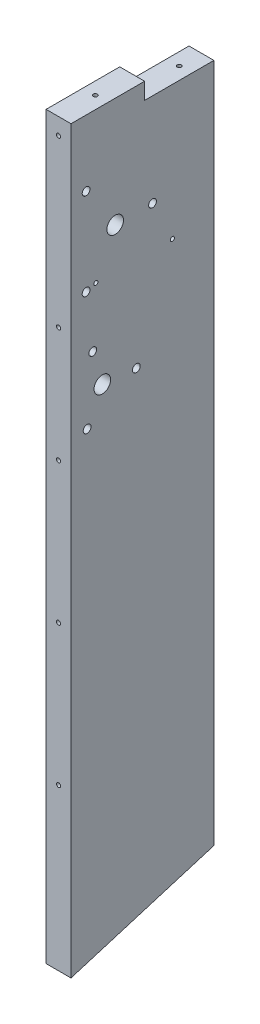
SolidWorks part; units mm, degrees
material "Beech"
ref_plane "Front Plane" through (0, 0, 0) normal (0, 0, 1) x (1, 0, 0)
ref_plane "Top Plane" through (0, 0, 0) normal (0, 1, 0) x (1, 0, 0)
ref_plane "Right Plane" through (0, 0, 0) normal (1, 0, 0) x (0, 0, -1)
sketch "Sketch1" plane through (0, 0, 0) normal (0, 0, 1) x (1, 0, 0)
  line L0 (-331.7795, -427.3421) -> (-331.7795, 0) construction
  line L1 (93.2955, -427.3421) -> (-341.3045, -427.3421) construction
  line L3 (-322.2545, -427.3421) -> (-322.2545, 0)
  line L4 (-341.3045, -427.3421) -> (-341.3045, 0)
  line L5 (-322.2545, -427.3421) -> (-341.3045, -427.3421)
  line L6 (-322.2545, 0) -> (-341.3045, 0)
  line L7 (-341.3045, -427.3421) -> (-341.3045, 12.7) construction
  line L8 (-331.7795, -427.3421) -> (-331.7795, 0) construction
  dimension "D1" = 19.05
extrude "Boss-Extrude1" add sketch "Sketch1" along normal up to surface (53 mm away)
sketch "Sketch2" plane through (0, 0, 53) normal (0, 0, 1) x (1, 0, 0)
  line L0 (-231.3045, 12.7) -> (-341.3045, 12.7) construction
  line L1 (-322.2545, 12.7) -> (-341.3045, 12.7)
  line L4 (-341.3045, 0) -> (-341.3045, -427.3421)
  line L5 (-341.3045, -427.3421) -> (-322.2545, -427.3421)
  line L6 (-322.2545, -427.3421) -> (-322.2545, 0)
  line L7 (-322.2545, 0) -> (-341.3045, 0)
  line L8 (-341.3045, 12.7) -> (-341.3045, -427.3421)
  line L9 (-341.3045, -427.3421) -> (-322.2545, -427.3421)
  line L10 (-322.2545, -427.3421) -> (-322.2545, 12.7)
  dimension "D1" = 0
extrude "Boss-Extrude2" add sketch "Sketch2" along normal up to surface (56.3 mm away)
sketch "Sketch3" plane through (-341.3045, 0, 0) normal (-1, 0, 0) x (0, 0, 1)
  line L0 (0, -427.3421) -> (109.3, -427.3421)
  line L1 (109.3, -427.3421) -> (109.3, -464.2661)
  line L2 (109.3, -464.2661) -> (0, -431.1858)
  line L3 (-12.7, -427.3421) -> (522.1409, -589.2145) construction
  line L4 (0, -431.1858) -> (0, -427.3421)
extrude "Boss-Extrude3" add sketch "Sketch3" against normal through all
hole_wizard "15/64 (0.23438) Diameter Hole1" positions "Sketch5" profile "Sketch6" hole size "15/64" standard "ANSI Inch" end condition through all
sketch "Sketch5" plane through (-341.3045, 0, 0) normal (-1, 0, 0) x (0, 0, 1)
  point P0 (97.7483, -37.836)
  point P3 (97.7483, -104.511)
  point P6 (46.9483, -71.1735)
  point P9 (92.6826, -146.5881)
  point P12 (96.9737, -195.6358)
  point P15 (59.3512, -174.2158)
sketch "Sketch6" plane through (-341.3045, -37.836, 97.7483) normal (0, 1, 0) x (0, 0, 1)
  line L0 (0, 0) -> (0, 19.05)
  line L1 (0, 19.05) -> (2.9766, 19.05)
  line L2 (2.9766, 19.05) -> (2.9766, 0)
  line L5 (2.9766, 0) -> (0, 0)
  line L11 (0, -6.35) -> (0, 107.95) construction
  dimension "Thru Hole Dia." = 5.9533
  dimension "Thru Hole Depth" = 19.05
sketch "Sketch4" plane through (-341.3045, 0, 0) normal (-1, 0, 0) x (0, 0, 1)
  circle A0 centre (75.5233, -71.1735) radius 6.35 construction
  circle A1 centre (75.5233, -71.1735) radius 6.35
  circle A2 centre (85.3394, -171.9421) radius 6.35 construction
  circle A3 centre (85.3394, -171.9421) radius 6.35
extrude "Cut-Extrude1" cut sketch "Sketch4" against normal through all
hole_wizard "Hole1" positions "Sketch7" profile "Sketch8" legacy
sketch "Sketch7" plane through (-124.0045, -78.4757, 122) normal (0, 0, 1) x (-1, 0, 0)
  line L1 (0, 465.9538) -> (0, 66.1243) construction
  line L2 (126.073, 146.2179) -> (113.373, 146.2179) construction
  line L6 (119.723, 195.4304) -> (119.723, 97.0054) construction
  line L10 (68.923, 196.0654) -> (68.923, 111.2929) construction
  point P1 (113.65, 39.9076)
  point P3 (113.65, -64.959)
  point P5 (-94.6, 72.4743)
  point P7 (94.6, 72.4743)
  point P9 (0, 72.4743)
  point P11 (0, 104.2243)
  point P13 (0, 351.6538)
  point P15 (0, 213.0704)
  point P17 (40.9792, 213.0704)
  point P19 (166.7958, 213.0704)
  point P21 (207.775, 351.6538)
  point P23 (207.775, 244.1214)
  point P25 (207.775, 136.589)
  point P27 (207.775, 48.5243)
  point P29 (207.775, -78.4757)
  point P33 (-207.775, -78.4757)
  point P34 (-207.775, 48.5243)
  point P35 (-207.775, 136.589)
  point P36 (-207.775, 244.1214)
  point P37 (-207.775, 351.6538)
  point P38 (-166.7958, 213.0704)
  point P39 (-40.9792, 213.0704)
  point P40 (-113.65, -64.959)
  point P41 (-113.65, 39.9076)
  point P58 (119.723, 146.2179)
  point P65 (119.723, 109.7054)
  point P68 (119.723, 182.7304)
  point P78 (18.123, 109.7054)
  point P79 (18.123, 182.7304)
  point P81 (0, 0)
  point P82 (113.65, 23.941)
  point P83 (0, 0)
  point P84 (207.775, -78.2752)
  point P85 (209.3058, -90.1558)
  point P86 (207.775, -78.4757)
  point P88 (113.65, -64.959)
  point P90 (207.775, 48.5243)
  point P92 (0, 0)
  point P93 (207.775, 136.589)
  point P95 (207.775, 244.1214)
  point P97 (207.775, 351.6538)
  point P99 (113.65, 39.9076)
  point P101 (94.6, 72.4743)
  point P103 (0, 72.4743)
  point P105 (0, 104.2243)
  point P107 (0, 0)
  point P108 (0, 213.0704)
  point P110 (0, 0)
  point P111 (0, 351.6538)
  point P113 (-40.9792, 213.0704)
  point P115 (-94.6, 72.4743)
  point P117 (-166.7958, 213.0704)
  point P119 (-113.65, -64.959)
  point P121 (0, 66.1243)
  dimension "D1" = 12.7
  dimension "D2" = 12.7
sketch "Sketch8" plane through (-237.6545, -118.3833, 122) normal (1, 0, 0) x (0, -1, 0)
  line L0 (0, 0) -> (0, 32.7039)
  line L1 (0, 32.7039) -> (1.5875, 31.75)
  line L2 (1.5875, 31.75) -> (1.5875, 4.0177)
  line L3 (1.5875, 4.0177) -> (5.08, 0)
  line L4 (5.08, 0) -> (0, 0)
  line L5 (0, -14.3089) -> (0, 102.4216) construction
  line L6 (0, 32.7039) -> (-1.5875, 31.75) construction
  line L7 (-1.5875, 4.0177) -> (-5.08, 0) construction
  dimension "Diameter" = 3.175
  dimension "Depth" = 31.75
  dimension "C-Sink Diameter" = 10.16
  dimension "C-Sink Angle" = 82
  dimension "Drill Angle" = 118
hole_wizard "Hole" positions "Sketch9" profile "Sketch10" legacy
sketch "Sketch9" plane through (-124.0045, 25.4, -155.2867) normal (0, 1, 0) x (-1, 0, 0)
  point P0 (113.65, 236.4367)
  point P2 (207.775, 236.4367)
sketch "Sketch10" plane through (-237.6545, 25.4, 81.15) normal (1, 0, 0) x (0, 0, 1)
  line L0 (0, 0) -> (0, 32.7039)
  line L1 (0, 32.7039) -> (1.5875, 31.75)
  line L2 (1.5875, 31.75) -> (1.5875, 4.0177)
  line L3 (1.5875, 4.0177) -> (5.08, 0)
  line L4 (5.08, 0) -> (0, 0)
  line L5 (0, -14.3089) -> (0, 102.4216) construction
  line L6 (0, 32.7039) -> (-1.5875, 31.75) construction
  line L7 (-1.5875, 4.0177) -> (-5.08, 0) construction
  dimension "Diameter" = 3.175
  dimension "Depth" = 31.75
  dimension "C-Sink Diameter" = 10.16
  dimension "C-Sink Angle" = 82
  dimension "Drill Angle" = 118
hole_wizard "Hole3" positions "Sketch12" profile "Sketch13" legacy
sketch "Sketch12" plane through (-124.0045, 12.7, -155.2867) normal (0, 1, 0) x (-1, 0, 0)
  line L0 (120, 172.2617) -> (217.3, 172.2617) construction
  point P8 (126.35, 172.2617)
  point P10 (207.775, 172.2617)
sketch "Sketch13" plane through (-331.7795, 12.7, 16.975) normal (1, 0, 0) x (0, 0, 1)
  line L0 (0, 0) -> (0, 32.7039)
  line L1 (0, 32.7039) -> (1.5875, 31.75)
  line L2 (1.5875, 31.75) -> (1.5875, 4.0177)
  line L3 (1.5875, 4.0177) -> (5.08, 0)
  line L4 (5.08, 0) -> (0, 0)
  line L5 (0, -14.3089) -> (0, 102.4216) construction
  line L6 (0, 32.7039) -> (-1.5875, 31.75) construction
  line L7 (-1.5875, 4.0177) -> (-5.08, 0) construction
  dimension "Diameter" = 3.175
  dimension "Depth" = 31.75
  dimension "C-Sink Diameter" = 10.16
  dimension "C-Sink Angle" = 82
  dimension "Drill Angle" = 118
hole_wizard "Hole4" positions "Sketch14" profile "Sketch15" legacy
sketch "Sketch14" plane through (-124.0045, -78.4757, -12.7) normal (0, 0, -1) x (1, 0, 0)
  line L12 (0, 0) -> (0, 66.1243) construction
  line L17 (120, -84.8257) -> (217.3, -84.8257) construction
  line L21 (-217.3, -84.8257) -> (-120, -84.8257) construction
  point P0 (-207.775, 244.1214)
  point P3 (-207.775, 136.589)
  point P6 (-207.775, 48.5243)
  point P9 (-185.55, -84.8257)
  point P12 (-151.75, -84.8257)
  point P15 (-94.6, 72.4743)
  point P21 (94.6, 72.4743)
  point P24 (151.75, -84.8257)
  point P27 (185.55, -84.8257)
  point P30 (207.775, 48.5243)
  point P33 (207.775, 136.589)
  point P36 (207.775, 244.1214)
  point P39 (166.7958, 213.0704)
  point P42 (40.9792, 213.0704)
  point P45 (-40.9792, 213.0704)
  point P48 (-166.7958, 213.0704)
  point P51 (0, 104.2243)
  point P54 (0, 213.0704)
  point P57 (0, 323.4664)
  point P80 (-126.35, 34.5243)
  point P82 (-126.35, -46.8757)
  point P96 (126.35, -46.8757)
  point P97 (126.35, 34.5243)
  dimension "D4" = 31.75
  dimension "D5" = 31.75
sketch "Sketch15" plane through (-331.7795, -322.5971, -12.7) normal (1, 0, 0) x (0, 1, 0)
  line L0 (0, 0) -> (0, 32.7039)
  line L1 (0, 32.7039) -> (1.5875, 31.75)
  line L2 (1.5875, 31.75) -> (1.5875, 4.0177)
  line L3 (1.5875, 4.0177) -> (5.08, 0)
  line L4 (5.08, 0) -> (0, 0)
  line L5 (0, -14.3089) -> (0, 102.4216) construction
  line L6 (0, 32.7039) -> (-1.5875, 31.75) construction
  line L7 (-1.5875, 4.0177) -> (-5.08, 0) construction
  dimension "Diameter" = 3.175
  dimension "Depth" = 31.75
  dimension "C-Sink Diameter" = 10.16
  dimension "C-Sink Angle" = 82
  dimension "Drill Angle" = 118
hole_wizard "Hole5" positions "Sketch16" profile "Sketch17" legacy rebuild error yes
sketch "Sketch16" plane through (-124.0045, -452.1296, -268.3751) normal (0, -0.9571, -0.2897) x (1, 0, 0)
  line L4 (-207.775, 822.0847) -> (-207.775, 404.0189) construction
  line L8 (-207.775, 822.0847) -> (-207.775, 717.5683)
  line L9 (-207.775, 717.5683) -> (-207.775, 613.0518)
  line L10 (-207.775, 613.0518) -> (-207.775, 508.5353)
  line L11 (-207.775, 508.5353) -> (-207.775, 404.0189)
  line L12 (-108.65, 822.0847) -> (-108.65, 404.0189) construction
  line L15 (0, 822.0847) -> (0, 613.0518) construction
  line L18 (-207.775, 388.2192) -> (-207.775, 263.2847) construction
  line L22 (-207.775, 388.2192) -> (-207.775, 356.9856)
  line L23 (-207.775, 356.9856) -> (-207.775, 325.752)
  line L24 (-207.775, 325.752) -> (-207.775, 294.5183)
  line L25 (-207.775, 294.5183) -> (-207.775, 263.2847)
  line L26 (0, 388.2192) -> (0, 263.2847) construction
  line L30 (0, 263.2847) -> (0, 294.5183)
  line L31 (0, 294.5183) -> (0, 325.752)
  line L32 (0, 325.752) -> (0, 356.9856)
  line L33 (0, 356.9856) -> (0, 388.2192)
  point P24 (-207.775, 613.0518)
  point P31 (-207.775, 456.2771)
  point P33 (-207.775, 769.8265)
  point P52 (-108.65, 456.2771)
  point P54 (-108.65, 630.1265)
  point P56 (-108.65, 769.8265)
  point P76 (-207.775, 356.9856)
  point P80 (-207.775, 294.5183)
  point P99 (0, 294.5183)
  point P104 (0, 356.9856)
  point P113 (207.775, 294.5183)
  point P114 (207.775, 356.9856)
  point P115 (108.65, 769.8265)
  point P116 (108.65, 630.1265)
  point P117 (108.65, 456.2771)
  point P118 (207.775, 769.8265)
  point P119 (207.775, 456.2771)
  point P120 (207.775, 613.0518)
  dimension "D1" = 139.7
sketch "Sketch17" plane through (83.7705, -629.7176, 318.3915) normal (1, 0, 0) x (0, 0.2897, -0.9571)
  line L0 (0, 0) -> (0, 32.7039)
  line L1 (0, 32.7039) -> (1.5875, 31.75)
  line L2 (1.5875, 31.75) -> (1.5875, 4.0177)
  line L3 (1.5875, 4.0177) -> (5.08, 0)
  line L4 (5.08, 0) -> (0, 0)
  line L5 (0, -14.3089) -> (0, 102.4216) construction
  line L6 (0, 32.7039) -> (-1.5875, 31.75) construction
  line L7 (-1.5875, 4.0177) -> (-5.08, 0) construction
  dimension "Diameter" = 3.175
  dimension "Depth" = 31.75
  dimension "C-Sink Diameter" = 10.16
  dimension "C-Sink Angle" = 82
  dimension "Drill Angle" = 118
hole_wizard "Hole6" positions "Sketch18" profile "Sketch19" legacy
sketch "Sketch18" plane through (-354.0045, -78.4757, -155.2867) normal (-1, 0, 0) x (0, -0.9959, 0.09)
  line L0 (47.5949, 261.3648) -> (37.7623, 152.508) construction
  line L6 (451.4691, 193.1171) -> (418.4769, 118.1196) construction
  line L11 (486.2923, 274.2447) -> (514.0528, 264.0879) construction
  line L16 (472.4376, 447.6352) -> (491.8067, 432.4853) construction
  line L19 (635.9114, 629.7221) -> (595.5648, 529.8608) construction
  line L24 (664.0363, 618.3589) -> (454.7061, 100.2486) construction
  line L28 (664.0363, 618.3589) -> (611.7037, 488.8313)
  line L29 (611.7037, 488.8313) -> (559.3712, 359.3037)
  line L30 (559.3712, 359.3037) -> (507.0387, 229.7761)
  line L31 (507.0387, 229.7761) -> (454.7061, 100.2486)
  point P12 (45.8811, 242.3921)
  point P14 (40.6185, 184.1293)
  point P29 (426.1478, 135.557)
  point P31 (446.3552, 181.4922)
  point P48 (500.1726, 269.1663)
  point P79 (628.7751, 612.0592)
  point P81 (602.701, 547.5236)
  point P98 (559.3712, 359.3037)
  point P100 (507.0387, 229.7761)
  point P112 (637.87, 553.5951)
  point P120 (0, 0)
  dimension "D1" = 19.05
  dimension "D2" = 31.75
  dimension "D3" = 12.7
  dimension "D4" = 19.05
  dimension "D5" = 19.05
  dimension "D6" = 19.05
sketch "Sketch19" plane through (-354.0045, -663.9582, 453.4463) normal (0, 1, 0) x (0, 0, 1)
  line L0 (0, 0) -> (0, 32.7039)
  line L1 (0, 32.7039) -> (1.5875, 31.75)
  line L2 (1.5875, 31.75) -> (1.5875, 4.0177)
  line L3 (1.5875, 4.0177) -> (5.08, 0)
  line L4 (5.08, 0) -> (0, 0)
  line L5 (0, -14.3089) -> (0, 102.4216) construction
  line L6 (0, 32.7039) -> (-1.5875, 31.75) construction
  line L7 (-1.5875, 4.0177) -> (-5.08, 0) construction
  dimension "Diameter" = 3.175
  dimension "Depth" = 31.75
  dimension "C-Sink Diameter" = 10.16
  dimension "C-Sink Angle" = 82
  dimension "Drill Angle" = 118
sketch "Sketch20" plane through (0, -395.0034, -119.5499) normal (0, -0.9571, -0.2897) x (1, 0, 0)
  line L4 (-341.3045, 239.1016) -> (-341.3045, 124.9053)
  line L5 (-341.3045, 124.9053) -> (-322.2545, 124.9053)
  line L6 (-322.2545, 124.9053) -> (-322.2545, 239.1016)
  line L7 (-322.2545, 239.1016) -> (-341.3045, 239.1016)
  line L8 (-341.3045, 239.1016) -> (-341.3045, 124.9053)
  line L9 (-341.3045, 124.9053) -> (-322.2545, 124.9053)
  line L10 (-322.2545, 124.9053) -> (-322.2545, 239.1016)
  line L11 (-322.2545, 239.1016) -> (-341.3045, 239.1016)
  dimension "D1" = 0
extrude "Boss-Extrude4" add sketch "Sketch20" along direction (0, 1, 0) on the side of the normal blind 88.9
